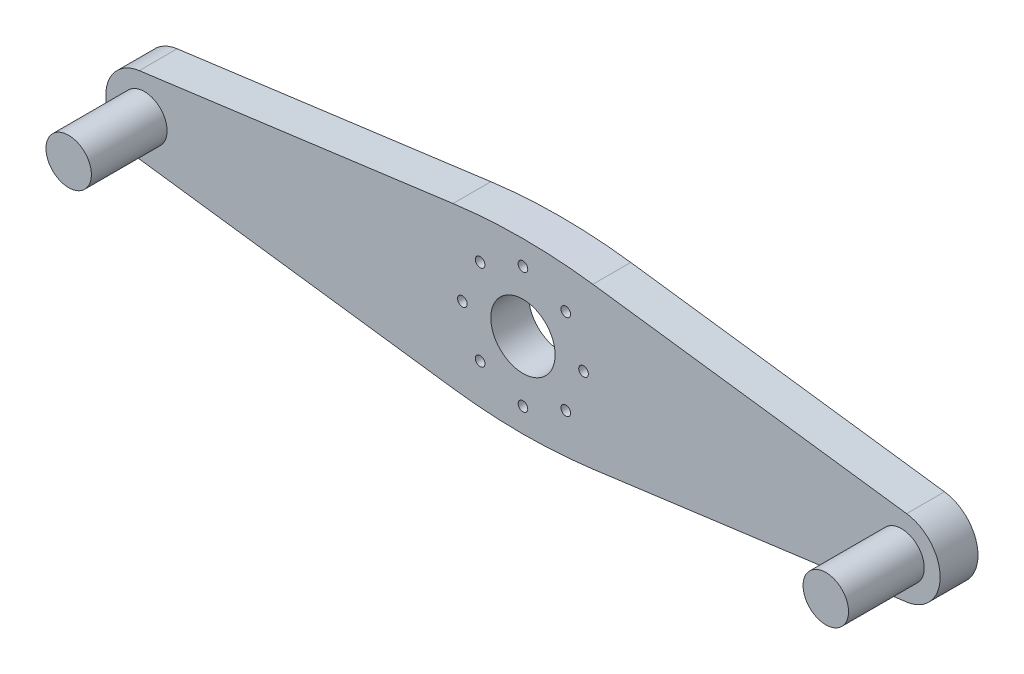
SolidWorks part; units mm, degrees
material "ABS"
ref_plane "Płaszczyzna przednia" through (0, 0, 0) normal (0, 0, 1) x (1, 0, 0)
ref_plane "Płaszczyzna górna" through (0, 0, 0) normal (0, 1, 0) x (1, 0, 0)
ref_plane "Płaszczyzna prawa" through (0, 0, 0) normal (1, 0, 0) x (0, 0, -1)
sketch "Szkic1" plane through (0, 0, 0) normal (0, 0, 1) x (1, 0, 0)
  line L0 (-44.521, 0) -> (57.4684, 0) construction
  line L1 (0, 0) -> (0, 26.3225) construction
  line L2 (-50.6729, 5.0557) -> (-9.2351, 10.5708)
  line L3 (-50.6729, -5.0557) -> (-9.2351, -10.5708)
  line L4 (50.6729, -5.0557) -> (9.2351, -10.5708)
  line L5 (50.6729, 5.0557) -> (9.2351, 10.5708)
  circle A0 centre (0, 0) radius 4.25
  circle A1 centre (-5.6569, 5.6569) radius 0.635
  circle A2 centre (-8, 0) radius 0.635
  circle A3 centre (0, 8) radius 0.635
  circle A4 centre (5.6569, 5.6569) radius 0.635
  circle A5 centre (-50, 0) radius 3
  circle A6 centre (50, 0) radius 3
  arc A7 (-50.6729, 5.0557) -> (-50.6729, -5.0557) centre (-50, 0) ccw
  arc A8 (50.6729, 5.0557) -> (50.6729, -5.0557) centre (50, 0) cw
  arc A9 (-9.2351, 10.5708) -> (9.2351, 10.5708) centre (0, -58.8174) cw
  arc A10 (-9.2351, -10.5708) -> (9.2351, -10.5708) centre (0, 58.8174) ccw
  circle A11 centre (8, 0) radius 0.635
  circle A12 centre (5.6569, -5.6569) radius 0.635
  circle A13 centre (0, -8) radius 0.635
  circle A14 centre (-5.6569, -5.6569) radius 0.635
  point P16 (0, 0)
  point P28 (0, 11.7999)
  point P31 (0, -11.7999)
  point P41 (0, 0)
  dimension "D1" = 8
  dimension "D2" = 50
  dimension "D3" = 8.5
  dimension "D4" = 6
  dimension "D5" = 1.27
  dimension "D7" = 70
  dimension "D8" = 21.1415
extrude "Dodanie-wyciągnięcie1" add sketch "Szkic1" along normal blind 5
extrude "Dodanie-wyciągnięcie2" add sketch "Szkic1<2>" along normal blind 15 contours A5 | A6 region at (-50, 0, 0) region at (50, 0, 0)
sketch "Szkic1<2>" plane through (0, 0, 0) normal (0, 0, 1) x (1, 0, 0) same geometry as "Szkic1"
